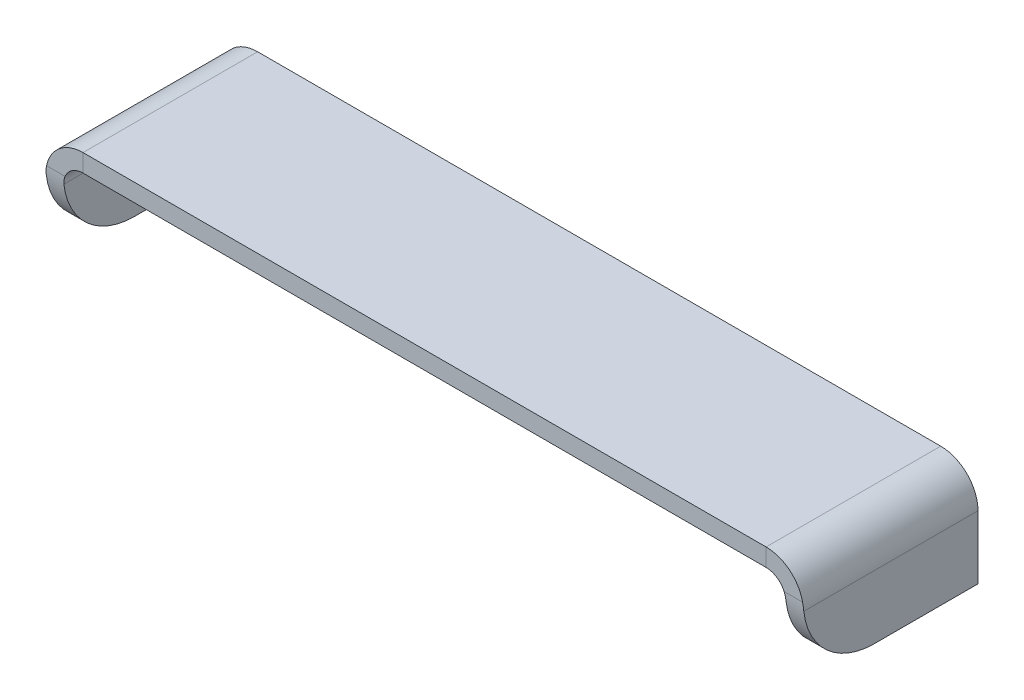
SolidWorks part; units mm, degrees
note: The reader was unsure of these and kept them because the rebuilt part matched: flange length of "Edge-Flange1".
ref_plane "Front" through (0, 0, 0) normal (0, 0, 1) x (1, 0, 0)
ref_plane "Top" through (0, 0, 0) normal (0, 1, 0) x (1, 0, 0)
ref_plane "Right" through (0, 0, 0) normal (1, 0, 0) x (0, 0, -1)
sketch "Sketch1" plane through (0, 0, 0) normal (0, 1, 0) x (1, 0, 0)
  line L1 (0, 0) -> (64, 0)
  line L2 (0, 0) -> (0, 14.75)
  line L3 (0, 14.75) -> (64, 14.75)
  line L4 (64, 0) -> (64, 14.75)
  dimension "D1" = 14.75
  dimension "D2" = 64
base flange "Base-Flange1" sketch "Sketch1" thickness 1.5 reverse thickness direction no parameters "D1"=1.65
edge flange "Edge-Flange1" sketch "Sketch10" flange profiles "Sketch10", "Sketch11" flange angle 90 flange length 7 flange position material inside bend radius 1.65 thickness 1.5 relief rectangular parameters "D6"=10, "D8"=1
sketch "Sketch10" plane through (0, -1.5, 0) normal (-1, 0, 0) x (0, 0, -1)
  line L2 (0, 0) -> (0, 7)
  line L3 (0, 7) -> (14.75, 7)
  line L4 (14.75, 7) -> (14.75, 0)
  line L7 (14.75, 0) -> (0, 0) construction
  line L8 (14.75, 0) -> (0, 0)
sketch "Sketch11" plane through (64, -1.5, 0) normal (1, 0, 0) x (0, 0, 1)
  line L0 (0, 0) -> (-14.75, 0) construction
  line L1 (0, 0) -> (-14.75, 0)
  line L2 (-14.75, 0) -> (-14.75, 7)
  line L3 (-14.75, 7) -> (0, 7)
  line L4 (0, 7) -> (0, 0)
bend "EdgeBend1" bend radius 1.65 bend angle 90 parameters "D5"=1
bend "EdgeBend2" bend radius 1.65 bend angle 90 parameters "D5"=2
fillet "Fillet1" radius 6 2 edges at (0.75, -8.5, 0) (63.25, -8.5, 0)
sketch "Bend-Lines1" [suppressed] plane through (0, 0, 0) normal (0, 1, 0) x (1, 0, 0)
sketch "Bounding-Box1" [suppressed] plane through (0, 0, 0) normal (0, 1, 0) x (1, 0, 0)
sheet metal parameters "Sheet-Metal1" thickness 1.5 parameters "D1"=1.65
flat pattern "Flat-Pattern1" [suppressed]
sketch "Bend-Lines2" plane through (0, 0, 0) normal (0, 1, 0) x (1, 0, 0)
sketch3d "Bounding-Box2" [suppressed]
  line L0 (50.9379, 14.75, 0) -> (0, 14.75, 0) construction
  line L1 (50.9379, 0, 0) -> (0, 0, 0) construction
  line L2 (50.9379, 14.75, 0) -> (50.9379, 0, 0) construction
  line L3 (0, 14.75, 0) -> (0, 0, 0) construction
sheet metal parameters "Sheet-Metal2" thickness 1.5 parameters "D1"=1.65
flat pattern "Flat-Pattern1"
sketch "Bend-Lines2" plane through (0, 0, 0) normal (0, 1, 0) x (1, 0, 0)
  line L0 (62.735, 0) -> (62.735, 14.75) construction
  line L1 (1.265, 14.75) -> (1.265, 0) construction
  line L2 (62.735, 0) -> (62.735, 14.75) construction
  line L3 (1.265, 14.75) -> (1.265, 0) construction
sketch3d "Bounding-Box2" [suppressed]
  line L0 (-5.9699, 14.75, 0) -> (69.9699, 14.75, 0) construction
  line L1 (-5.9699, 0, 0) -> (69.9699, 0, 0) construction
  line L2 (-5.9699, 14.75, 0) -> (-5.9699, 0, 0) construction
  line L3 (69.9699, 14.75, 0) -> (69.9699, 0, 0) construction
bend of the flat pattern "Flatten-<EdgeBend1>1"
bend of the flat pattern "Flatten-<EdgeBend2>1"
equation "\"chipper width\"= 67mm"
equation "\"D2@Sketch1\"=\"chipper width\"-2*\"Thickness\""
